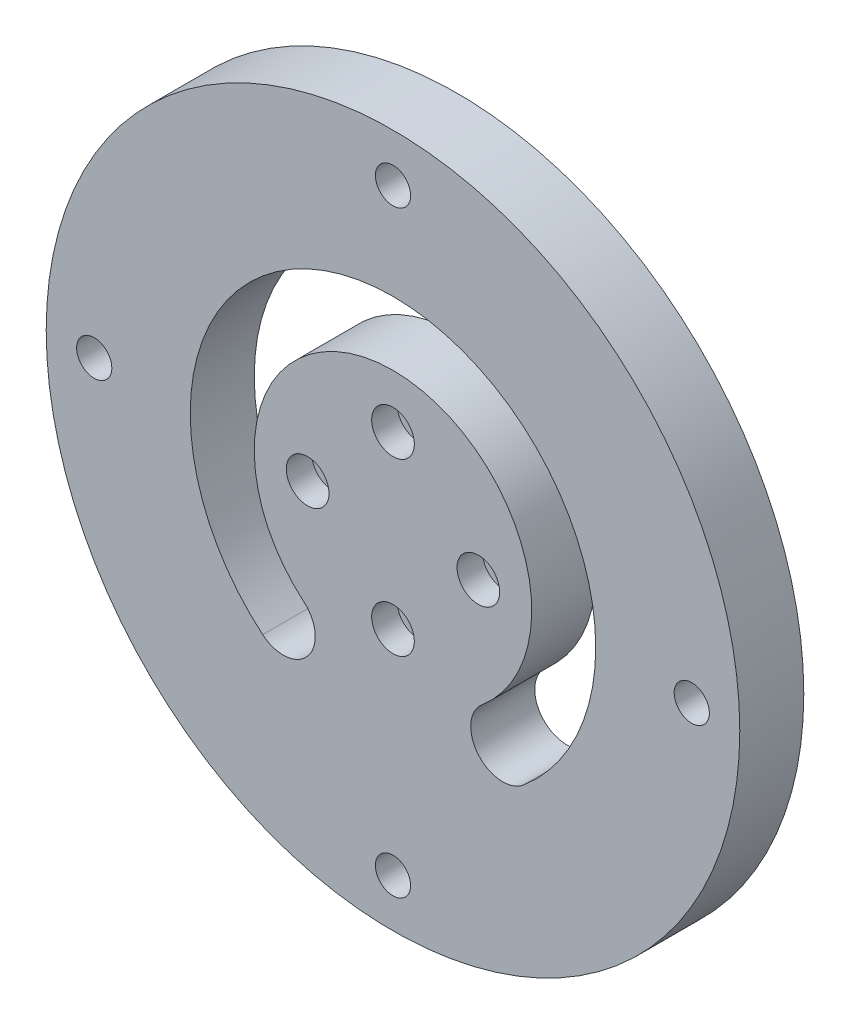
SolidWorks part; units mm, degrees
ref_plane "Front Plane" through (0, 0, 0) normal (0, 0, 1) x (1, 0, 0)
ref_plane "Top Plane" through (0, 0, 0) normal (0, 1, 0) x (1, 0, 0)
ref_plane "Right Plane" through (0, 0, 0) normal (1, 0, 0) x (0, 0, -1)
sketch "Sketch1" plane through (0, 0, 0) normal (0, 0, 1) x (1, 0, 0)
  circle A0 centre (0, 0) radius 32.5
  dimension "D1" = 65
extrude "Boss-Extrude1" add sketch "Sketch1" along normal blind 6
sketch "Sketch16" plane through (0, 0, 6) normal (0, 0, 1) x (1, 0, 0)
  line L0 (-8, 0) -> (8, 0) construction
  line L1 (0, 0) -> (0, -8) construction
  line L2 (0, 0) -> (0, 8) construction
  circle A0 centre (8, 0) radius 1.1
  circle A1 centre (-8, 0) radius 1.1
  circle A2 centre (0, -8) radius 1.1
  circle A3 centre (0, 8) radius 1.1
  point P6 (0, 0)
  dimension "D1" = 2.2
  dimension "D2" = 8
  dimension "D3" = 16
  dimension "D4" = 8
extrude "Cut-Extrude8" cut sketch "Sketch16" against normal through all
sketch "Sketch17" plane through (0, 0, 6) normal (0, 0, 1) x (1, 0, 0)
  circle A0 centre (8, 0) radius 2
  circle A1 centre (-8, 0) radius 2
  circle A2 centre (0, -8) radius 2
  circle A3 centre (0, 8) radius 2
  dimension "D1" = 4
extrude "Cut-Extrude9" cut sketch "Sketch17" against normal blind 2.4
sketch "Sketch12" plane through (0, 0, 6) normal (0, 0, 1) x (1, 0, 0)
  line L0 (0, 0) -> (0, 28) construction
  circle A4 centre (0, 28) radius 1.65
  circle A5 centre (28, 0) radius 1.65
  circle A6 centre (0, -28) radius 1.65
  circle A7 centre (-28, 0) radius 1.65
  point P14 (0, 0)
  dimension "D3" = 4
  dimension "D1" = 3.3
  dimension "D2" = 28
extrude "Cut-Extrude10" cut sketch "Sketch12" against normal through all
sketch "Sketch18" plane through (0, 0, 0) normal (0, 0, -1) x (-1, 0, 0)
  line L1 (1.6166, 30.8) -> (-1.6166, 30.8)
  line L2 (-1.6166, 30.8) -> (-3.2332, 28)
  line L3 (-3.2332, 28) -> (-1.6166, 25.2)
  line L4 (-1.6166, 25.2) -> (1.6166, 25.2)
  line L5 (1.6166, 25.2) -> (3.2332, 28)
  line L6 (3.2332, 28) -> (1.6166, 30.8)
  line L7 (29.6166, 2.8) -> (26.3834, 2.8)
  line L8 (26.3834, 2.8) -> (24.7668, 0)
  line L9 (24.7668, 0) -> (26.3834, -2.8)
  line L10 (26.3834, -2.8) -> (29.6166, -2.8)
  line L11 (29.6166, -2.8) -> (31.2332, 0)
  line L12 (31.2332, 0) -> (29.6166, 2.8)
  line L13 (1.6166, -25.2) -> (-1.6166, -25.2)
  line L14 (-1.6166, -25.2) -> (-3.2332, -28)
  line L15 (-3.2332, -28) -> (-1.6166, -30.8)
  line L16 (-1.6166, -30.8) -> (1.6166, -30.8)
  line L17 (1.6166, -30.8) -> (3.2332, -28)
  line L18 (3.2332, -28) -> (1.6166, -25.2)
  line L19 (-26.3834, 2.8) -> (-29.6166, 2.8)
  line L20 (-29.6166, 2.8) -> (-31.2332, 0)
  line L21 (-31.2332, 0) -> (-29.6166, -2.8)
  line L22 (-29.6166, -2.8) -> (-26.3834, -2.8)
  line L23 (-26.3834, -2.8) -> (-24.7668, 0)
  line L24 (-24.7668, 0) -> (-26.3834, 2.8)
  circle A0 centre (0, 28) radius 2.8 construction
  circle A1 centre (28, 0) radius 2.8 construction
  circle A2 centre (0, -28) radius 2.8 construction
  circle A3 centre (-28, 0) radius 2.8 construction
  dimension "D1" = 5.6
extrude "Cut-Extrude11" cut sketch "Sketch18" against normal blind 3
sketch "Sketch19" plane through (0, 0, 6) normal (0, 0, 1) x (1, 0, 0)
  line L0 (0, 0) -> (0, -19.652) construction
  line L1 (0, 0) -> (12.213, -14.5548) construction
  line L2 (0, 0) -> (-12.213, -14.5548) construction
  arc A0 (12.213, -14.5548) -> (-12.213, -14.5548) centre (0, 0) ccw
  arc A1 (8.3562, -9.9586) -> (-8.3562, -9.9586) centre (0, 0) ccw
  arc A2 (-12.213, -14.5548) -> (-8.3562, -9.9586) centre (-10.2846, -12.2567) ccw
  arc A3 (8.3562, -9.9586) -> (12.213, -14.5548) centre (10.2846, -12.2567) ccw
  dimension "D1" = 6
  dimension "D3" = 13
  dimension "D2" = 40
extrude "Cut-Extrude12" cut sketch "Sketch19" against normal through all
